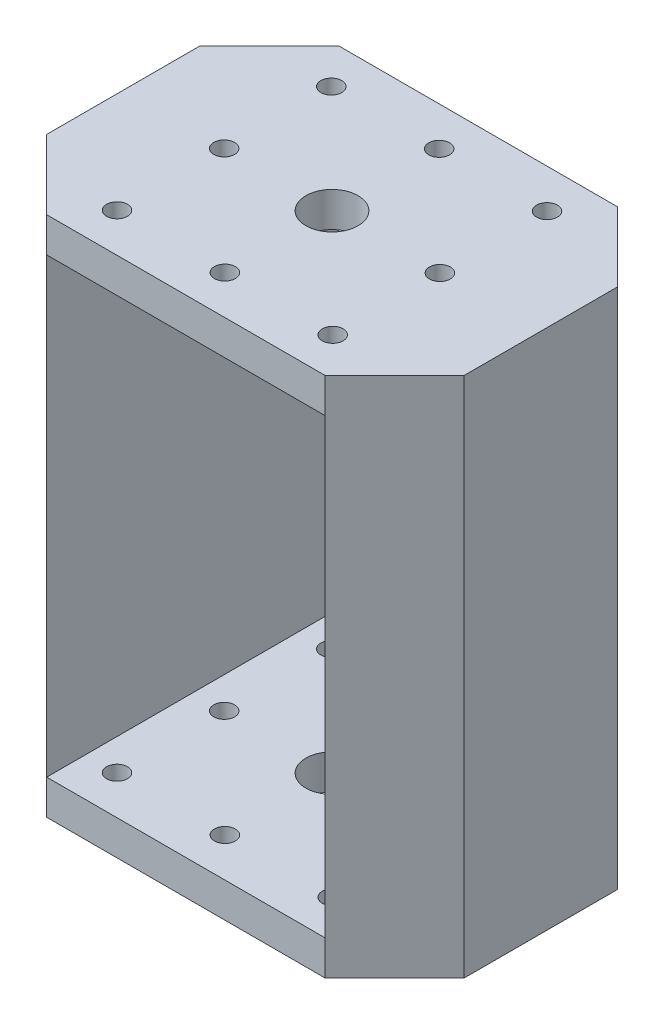
SolidWorks part; units mm, degrees
ref_plane "Front Plane" through (0, 0, 0) normal (0, 0, 1) x (1, 0, 0)
ref_plane "Top Plane" through (0, 0, 0) normal (0, 1, 0) x (1, 0, 0)
ref_plane "Right Plane" through (0, 0, 0) normal (1, 0, 0) x (0, 0, -1)
sketch "Sketch3" plane through (0, 0, 0) normal (0, 1, 0) x (1, 0, 0)
  line L0 (0, 0) -> (30, 0) construction
  line L1 (0, 0) -> (60, 0)
  line L2 (0, 0) -> (0, 42)
  line L3 (0, 42) -> (60, 42)
  line L4 (60, 0) -> (60, 42)
  line L5 (30, 0) -> (30, 42) construction
  line L6 (30, 0) -> (8.9, 0) construction
  line L7 (8.9, 0) -> (8.9, 42) construction
  line L8 (8.9, 42) -> (51.1, 42) construction
  line L9 (51.1, 42) -> (51.1, 0) construction
  line L10 (51.1, 0) -> (29.5942, 0) construction
  line L11 (8.9, 0) -> (14.5, 0) construction
  line L12 (14.5, 0) -> (14.5, 5.6) construction
  line L13 (51.1, 0) -> (45.5, 0) construction
  line L14 (45.5, 0) -> (45.5, 5.6) construction
  line L15 (9.2129, 42) -> (14.5, 42) construction
  line L16 (14.5, 42) -> (14.5, 36.4) construction
  line L17 (51.1, 42) -> (45.5, 42) construction
  line L18 (45.5, 42) -> (45.5, 36.4) construction
  line L19 (14.5, 5.6) -> (45.5, 5.6) construction
  line L20 (45.5, 5.6) -> (45.5, 36.4) construction
  line L21 (45.5, 36.4) -> (14.5, 36.4) construction
  line L22 (14.5, 5.6) -> (14.5, 36.4) construction
  circle A0 centre (30, 21) radius 3.75
  circle A1 centre (14.5, 36.4) radius 1.5
  circle A2 centre (45.5, 36.4) radius 1.5
  circle A3 centre (45.5, 5.6) radius 1.5
  circle A4 centre (14.5, 5.6) radius 1.5
  circle A5 centre (30, 36.4) radius 1.5
  circle A6 centre (45.5, 21) radius 1.5
  circle A7 centre (30, 5.6) radius 1.5
  circle A8 centre (14.5, 21) radius 1.5
  dimension "D3" = 5.6
  dimension "D5" = 7.5
  dimension "D1" = 60
  dimension "D2" = 42
  dimension "D4" = 5.6
  dimension "D6" = 30.8
  dimension "D7" = 31
extrude "Boss-Extrude1" add sketch "Sketch3" along normal blind 75
sketch "Sketch4" plane through (0, 0, -42) normal (0, 0, -1) x (-1, 0, 0)
  line L0 (-60, 75) -> (-60, 70) construction
  line L1 (-60, 75) -> (-60, 0) construction
  line L2 (-60, 75) -> (0, 75) construction
  line L3 (-60, 70) -> (0, 70) construction
  line L4 (0, 75) -> (0, 0) construction
  line L5 (0, 70) -> (0, 5)
  line L6 (0, 5) -> (-60, 5)
  line L7 (-60, 0) -> (0, 0) construction
  line L10 (-60, 5) -> (-60, 70)
  line L11 (-60, 70) -> (0, 70)
  dimension "D1" = 5
  dimension "D2" = 5
extrude "Cut-Extrude1" cut sketch "Sketch4" along direction (0, 0, -1) on the side against the normal through all
sketch "Sketch5" plane through (0, 5, 0) normal (0, 1, 0) x (1, 0, 0)
  line L0 (60, 42) -> (0, 42) construction
  line L1 (0, 0) -> (10, 0)
  line L2 (0, 0) -> (0, 42)
  line L3 (0, 42) -> (10, 42)
  line L6 (60, 0) -> (50, 0)
  line L7 (60, 0) -> (60, 42)
  line L8 (60, 42) -> (50, 42)
  line L9 (50, 2.5) -> (50, 39.5)
  line L10 (0, 42) -> (60, 42)
  line L11 (0, 42) -> (0, 0)
  line L13 (60, 42) -> (60, 39.5)
  line L14 (0, 0) -> (60, 0)
  line L15 (0, 0) -> (0, 2.5)
  line L17 (60, 0) -> (60, 2.5)
  line L18 (50, 39.5) -> (50, 42)
  line L19 (50, 2.5) -> (50, 0)
  line L20 (0, 42) -> (10, 42)
  line L21 (0, 42) -> (0, 0)
  line L22 (0, 0) -> (10, 0)
  line L23 (10, 42) -> (10, 0)
  dimension "D1" = 10
extrude "Boss-Extrude2" add sketch "Sketch5" along normal up to next
chamfer "Chamfer2" distance 10 angle 45 4 edges at (60, 37.5, -42) (60, 37.5, 0) (0, 37.5, 0) (0, 37.5, -42)
